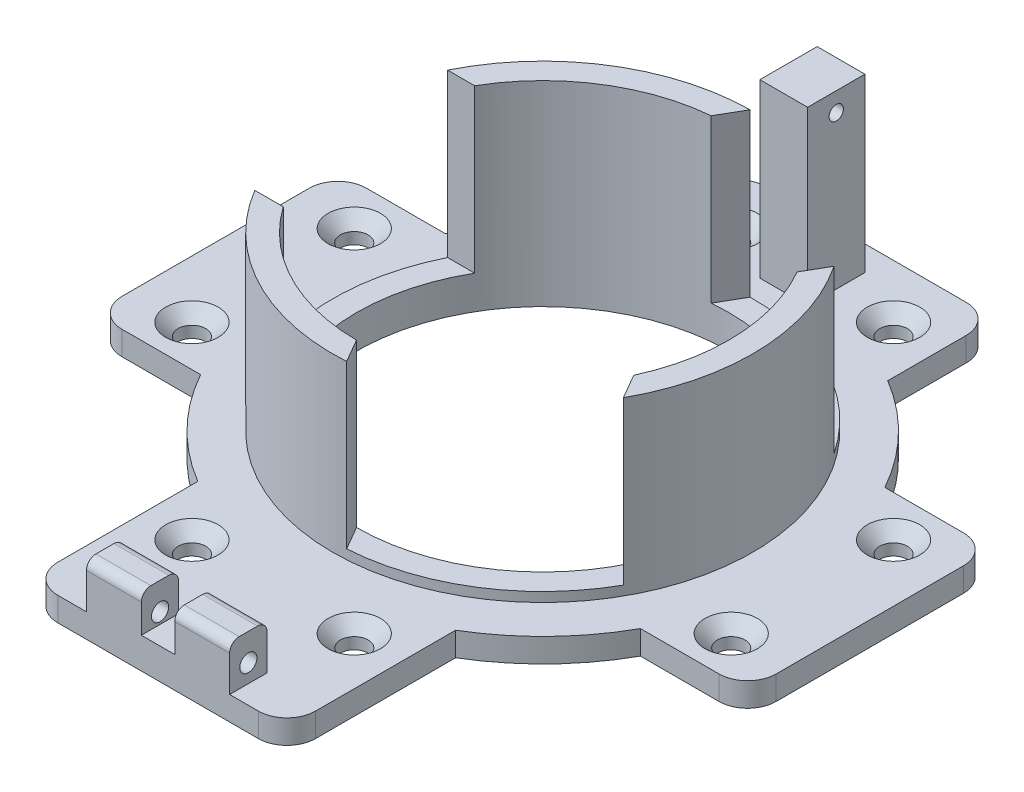
SolidWorks part; units mm, degrees
ref_plane "Front Plane" through (0, 0, 0) normal (0, 0, 1) x (1, 0, 0)
ref_plane "Top Plane" through (0, 0, 0) normal (0, 1, 0) x (1, 0, 0)
ref_plane "Right Plane" through (0, 0, 0) normal (1, 0, 0) x (0, 0, -1)
sketch "Sketch1" plane through (0, 0, 0) normal (0, 1, 0) x (1, 0, 0)
  line L1 (-34.2532, 12.8) -> (-23.0322, 12.8)
  line L2 (-34.2532, 12.8) -> (-34.2532, -12.8)
  line L3 (-34.2532, -12.8) -> (-23.0322, -12.8)
  line L4 (34.2532, 12.8) -> (34.2532, -12.8)
  line L7 (-13.5, 33.85) -> (13.5, 33.85)
  line L8 (-13.5, 33.85) -> (-13.5, 22.629)
  line L9 (-13.5, -40.29) -> (13.5, -40.29)
  line L10 (13.5, 33.85) -> (13.5, 22.629)
  line L14 (13.5, -22.629) -> (13.5, -40.29)
  line L15 (23.0322, -12.8) -> (34.2532, -12.8)
  line L16 (23.0322, 12.8) -> (34.2532, 12.8)
  line L19 (-13.5, -22.629) -> (-13.5, -40.29)
  circle A0 centre (0, 0) radius 19.5
  circle A1 centre (0, 0) radius 22
  arc A2 (-13.5, 22.629) -> (-23.0322, 12.8) centre (0, 0) ccw
  arc A3 (-23.0322, -12.8) -> (-13.5, -22.629) centre (0, 0) ccw
  arc A4 (23.0322, 12.8) -> (13.5, 22.629) centre (0, 0) ccw
  arc A5 (13.5, -22.629) -> (23.0322, -12.8) centre (0, 0) ccw
  dimension "D1" = 39
  dimension "D2" = 44
  dimension "D3" = 52.7
  dimension "D4" = 25.6
  dimension "D6" = 74.14
  dimension "D7" = 27
  dimension "D9" = 27.49
extrude "Boss-Extrude3" add sketch "Sketch1" along normal blind 2.5 contours L3 A3 L19 L9 L14 A5 L15 L4 L16 A4 L10 L7 L8 A2 L1 L2
extrude "Boss-Extrude4" add sketch "Sketch1<6>" along normal blind 20.5 contours A0 | A1
sketch "Sketch1<6>" plane through (0, 0, 0) normal (0, 1, 0) x (1, 0, 0) same geometry as "Sketch1"
sketch "Sketch33" plane through (0, 0, 0) normal (1, 0, 0) x (0, 0, -1)
  line L0 (-11.2463, 20.5) -> (9.7537, 20.5)
  line L1 (-11.2463, 20.5) -> (-11.2463, 3.5)
  line L2 (9.7537, 20.5) -> (9.7537, 3.5)
  line L3 (-11.2463, 3.5) -> (9.7537, 3.5)
  line L4 (19.5, 20.5) -> (-19.5, 20.5) construction
  line L5 (22, 20.5) -> (-22, 20.5) construction
  dimension "D1" = 17
  dimension "D2" = 21
extrude "Cut-Extrude2" cut sketch "Sketch33" against normal up to next contours L0 L1 L3 L2
pattern_circular "CirPattern1" count 3 every 120 about axis through (0, 20.5, 0) along (0, 1, 0) of "Cut-Extrude2"
extrude "Cut-Extrude1" cut sketch "Sketch1<7>" along normal blind 18 contours A0
sketch "Sketch1<7>" plane through (0, 0, 0) normal (0, 1, 0) x (1, 0, 0) same geometry as "Sketch1"
sketch "Sketch12" plane through (0, 2.5, 0) normal (0, 1, 0) x (1, 0, 0)
  line L0 (0, 0) -> (8.5, 28.2395) construction
  line L1 (-13.5, 33.85) -> (-13.5, 22.629) construction
  line L2 (13.5, 33.85) -> (13.5, 22.629) construction
  line L3 (0, 0) -> (28.2395, -8.5) construction
  line L4 (0, 0) -> (8.5, 28.2395) construction
  point P0 (-8.5, 28.2395)
  point P1 (8.5, 28.2395)
  point P8 (-13.5, 28.2395)
  point P10 (28.2395, 8.5)
  point P11 (28.2395, -8.5)
  point P12 (8.5, -28.2395)
  point P13 (-8.5, -28.2395)
  point P14 (-28.2395, -8.5)
  point P15 (-28.2395, 8.5)
  point P16 (0, 0)
  dimension "D1" = 5
  dimension "D2" = 5
  dimension "D4" = 90
  dimension "D5" = 29.491
  dimension "D3" = 4
hole_wizard "CSK for M2.5 Countersunk Flat Head Screw1" positions "Sketch13" profile "Sketch14" countersink size "M2.5" standard "ISO" end condition through all
sketch "Sketch13" plane through (0, 2.5, 0) normal (0, 1, 0) x (1, 0, 0)
  point P0 (-8.5, 28.2395)
  point P3 (8.5, 28.2395)
  point P6 (28.2395, 8.5)
  point P9 (28.2395, -8.5)
  point P12 (8.5, -28.2395)
  point P15 (-8.5, -28.2395)
  point P18 (-28.2395, 8.5)
  point P21 (-28.2395, -8.5)
sketch "Sketch14" plane through (-8.5, 2.5, -28.2395) normal (1, 0, 0) x (0, 0, 1)
  line L0 (0, 0) -> (0, 2.5)
  line L1 (0, 2.5) -> (1.45, 2.5)
  line L2 (1.45, 2.5) -> (1.45, 1.3)
  line L3 (1.45, 1.3) -> (2.75, 0)
  line L5 (2.75, 0) -> (0, 0)
  line L6 (-1.45, 1.3) -> (-2.75, 0) construction
  line L11 (0, -6.35) -> (0, 107.95) construction
  dimension "Thru Hole Dia." = 2.9
  dimension "Thru Hole Depth" = 2.5
  dimension "Near C'Sink Dia." = 5.5
  dimension "Near C'Sink Angle" = 90
sketch "Sketch15" plane through (0, 2.5, 0) normal (0, 1, 0) x (1, 0, 0)
  line L0 (-13.5, -40.29) -> (13.5, -40.29) construction
  line L1 (-7.5, -40.29) -> (-1.75, -40.29)
  line L2 (-7.5, -40.29) -> (-7.5, -36.4029)
  line L3 (-7.5, -36.4029) -> (-1.75, -36.4029)
  line L4 (-1.75, -40.29) -> (-1.75, -36.4029)
  line L5 (-13.5, -22.629) -> (-13.5, -40.29) construction
  line L6 (1.75, -40.29) -> (7.5, -40.29)
  line L7 (1.75, -40.29) -> (1.75, -36.3715)
  line L8 (1.75, -36.3715) -> (7.5, -36.3715)
  line L9 (7.5, -40.29) -> (7.5, -36.3715)
  line L10 (-1.75, -40.29) -> (1.75, -40.29)
  line L11 (-1.75, -40.29) -> (-1.75, -33.1745)
  line L12 (-1.75, -33.1745) -> (1.75, -33.1745)
  line L13 (1.75, -40.29) -> (1.75, -33.1745)
  line L14 (13.5, -22.629) -> (13.5, -40.29) construction
  line M26 (-13.5, -40.29) -> (13.5, -40.29)
  dimension "D1" = 6
  dimension "D2" = 5.75
  dimension "D3" = 6
  dimension "D4" = 5.75
  dimension "D5" = 3.5
extrude "Boss-Extrude5" add sketch "Sketch15" along normal blind 4.75 contours L9 L8 L7 M26 | L2 L1 L4 L3 region at (4.625, 2.5, 38.3307)
sketch "Sketch16" plane through (0, 2.5, 0) normal (0, 1, 0) x (1, 0, 0)
  line L1 (-1.75, -40.29) -> (1.75, -40.29)
  line L2 (-1.75, -40.29) -> (-1.75, -33.29)
  line L3 (-1.75, -33.29) -> (1.75, -33.29)
  line L4 (1.75, -40.29) -> (1.75, -33.29)
  dimension "D1" = 3.5
  dimension "D2" = 7
extrude "Boss-Extrude6" add sketch "Sketch16" along normal blind 0.75
fillet "Fillet1" radius 3 1 edges at (34.2532, 1.25, 12.8) type face fillet first side face at (34.2532, 1.25, 0) second side face at (28.6427, 1.25, 12.8)
fillet "Fillet2" radius 3 1 edges at (34.2532, 1.25, -12.8) type face fillet first side face at (34.2532, 1.25, -1.5) second side face at (28.6427, 1.25, -12.8)
fillet "Fillet3" radius 3 1 edges at (13.5, 1.25, -33.85) type face fillet first side face at (13.5, 1.25, -28.2395) second side face at (0, 1.25, -33.85)
fillet "Fillet4" radius 3 1 edges at (-13.5, 1.25, -33.85) type face fillet first side face at (-1.5, 1.25, -33.85) second side face at (-13.5, 1.25, -28.2395)
fillet "Fillet5" radius 3 1 edges at (-34.2532, 1.25, -12.8) type face fillet first side face at (-28.6427, 1.25, -12.8) second side face at (-34.2532, 1.25, 0)
fillet "Fillet6" radius 3 1 edges at (-34.2532, 1.25, 12.8) type face fillet first side face at (-34.2532, 1.25, 1.5) second side face at (-28.6427, 1.25, 12.8)
fillet "Fillet7" radius 3 1 edges at (-13.5, 1.25, 40.29) type face fillet first side face at (-13.5, 1.25, 31.4595) second side face at (0, 3.7917, 40.29)
fillet "Fillet8" radius 3 1 edges at (13.5, 1.25, 40.29) type face fillet first side face at (13.5, 1.25, 31.4595) second side face at (0.5, 3.7917, 40.29)
fillet "Fillet9" radius 1 1 edges at (-4.625, 7.25, 36.4029) type face fillet first side face at (-4.05, 4.55, 36.4029) second side face at (-4.625, 7.25, 38.3465)
fillet "Fillet10" radius 1 1 edges at (-4.625, 7.25, 40.29) type face fillet first side face at (0, 3.7917, 40.29) second side face at (-4.625, 7.25, 38.8465)
fillet "Fillet11" radius 1 1 edges at (4.625, 7.25, 40.29) type face fillet first side face at (0, 3.625, 40.29) second side face at (4.625, 7.25, 38.3307)
fillet "Fillet12" radius 1 1 edges at (4.625, 7.25, 36.3715) type face fillet first side face at (4.625, 7.25, 37.8307) second side face at (4.05, 4.55, 36.3715)
sketch "Sketch17" plane through (7.5, 0, 0) normal (1, 0, 0) x (0, 0, -1)
  line L0 (-40.29, 2.5) -> (-36.3715, 2.5) construction
  point P0 (-38.3307, 4.4)
  point P5 (-38.3307, 2.5)
  dimension "D1" = 1.9
hole_wizard "Ø1.8 (1.8) Diameter Hole2" positions "Sketch20" profile "Sketch21" hole size "Ø1.8" standard "ISO" end condition through all
sketch "Sketch20" plane through (7.5, 0, 0) normal (1, 0, 0) x (0, 0, -1)
  point P0 (-38.3307, 4.4)
sketch "Sketch21" plane through (7.5, 4.4, 38.3307) normal (0, 1, 0) x (0, 0, -1)
  line L0 (0, 0) -> (0, 41.7532)
  line L1 (0, 41.7532) -> (0.9, 41.7532)
  line L2 (0.9, 41.7532) -> (0.9, 0)
  line L5 (0.9, 0) -> (0, 0)
  line L11 (0, -6.35) -> (0, 107.95) construction
  dimension "Thru Hole Dia." = 1.8
  dimension "Thru Hole Depth" = 41.7532
sketch "Sketch22" plane through (0, 2.5, 0) normal (0, 1, 0) x (1, 0, 0)
  line L0 (-13.5, 33.85) -> (13.5, 33.85) construction
  line L1 (2.5, 25.2395) -> (-2.5, 25.2395)
  line L2 (2.5, 25.2395) -> (2.5, 31.2395)
  line L3 (2.5, 31.2395) -> (-2.5, 31.2395)
  line L4 (-2.5, 25.2395) -> (-2.5, 31.2395)
  point P4 (0, 31.2395)
  point P7 (0, 33.85)
  point P8 (2.5, 28.2395)
  dimension "D1" = 5
  dimension "D2" = 6
extrude "Boss-Extrude7" add sketch "Sketch22" along normal blind 18
sketch "Sketch26" plane through (-2.5, 0, 0) normal (-1, 0, 0) x (0, 0, 1)
  line L0 (-31.2395, 20.5) -> (-25.2395, 20.5) construction
  point P0 (-28.2395, 18.5)
  point P3 (-28.2395, 20.5)
  dimension "D1" = 2
hole_wizard "Ø1.5 (1.5) Diameter Hole1" positions "Sketch27" profile "Sketch28" hole size "Ø1.5" standard "ISO" end condition through all
sketch "Sketch27" plane through (-2.5, 0, 0) normal (-1, 0, 0) x (0, 0, 1)
  point P0 (-28.2395, 18.5)
sketch "Sketch28" plane through (-2.5, 18.5, -28.2395) normal (0, 1, 0) x (0, 0, 1)
  line L0 (0, 0) -> (0, 36.7532)
  line L1 (0, 36.7532) -> (0.75, 36.7532)
  line L2 (0.75, 36.7532) -> (0.75, 0)
  line L5 (0.75, 0) -> (0, 0)
  line L11 (0, -6.35) -> (0, 107.95) construction
  dimension "Thru Hole Dia." = 1.5
  dimension "Thru Hole Depth" = 36.7532
